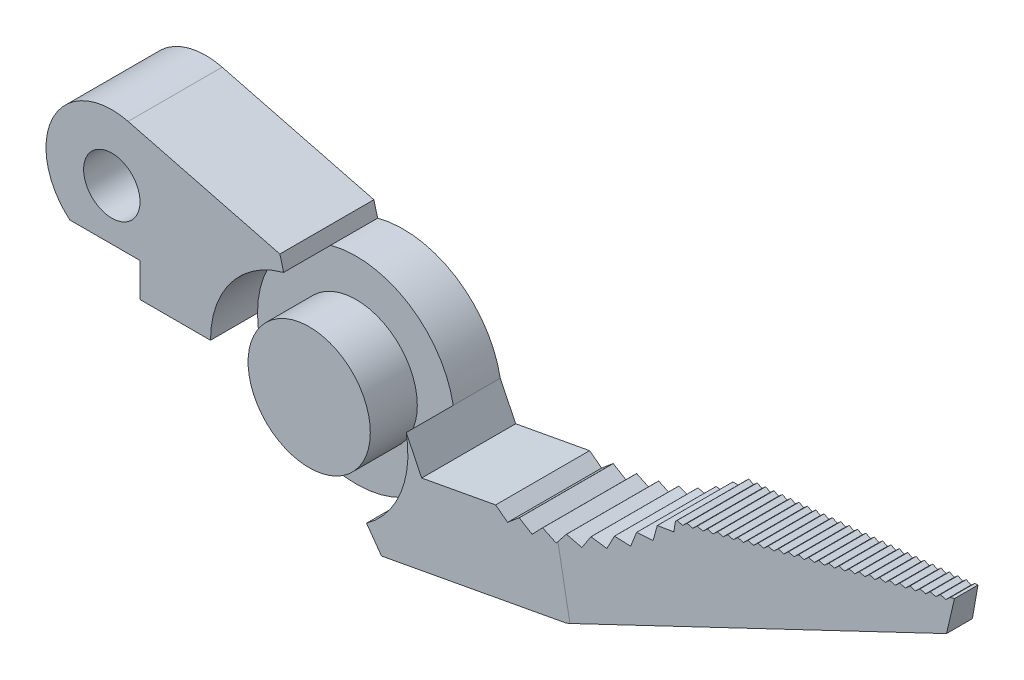
SolidWorks part; units mm, degrees
note: The reader was unsure of these and kept them because the rebuilt part matched: shared geometry of "Sketch1<3>", "Sketch1<4>".
ref_plane "Front Plane" through (0, 0, 0) normal (0, 0, 1) x (1, 0, 0)
ref_plane "Top Plane" through (0, 0, 0) normal (0, 1, 0) x (1, 0, 0)
ref_plane "Right Plane" through (0, 0, 0) normal (1, 0, 0) x (0, 0, -1)
sketch "Sketch1" plane through (0, 0, 0) normal (0, 0, 1) x (1, 0, 0)
  line L0 (-9.6304, 7.8902) -> (-1.5595, 5.82)
  line L2 (0, 0) -> (-1.5595, 5.82)
  line L3 (19.8321, 0) -> (0, 0) construction
  line L4 (0, 0) -> (0, 10.7679) construction
  line L5 (-12.7271, 1.8) -> (-9, 1.8)
  line L6 (-9, 1.8) -> (-9, 0)
  line L7 (-9, 0) -> (0, 0)
  line L8 (0, 0) -> (32.4474, 6.0138) construction
  line L9 (0, 0) -> (3.8444, -5.3897)
  line L10 (3.8444, -5.3897) -> (13.677, -3.5673)
  line L11 (13.677, -3.5673) -> (32.0857, 4.2505)
  line L12 (32.0857, 4.2505) -> (32.4474, 6.0138)
  line L13 (32.4474, 6.0138) -> (18.6818, 3.4625)
  line L14 (0, 0) -> (5.1621, 0.9567)
  line L15 (5.1621, 0.9567) -> (5.983, -0.7289)
  line L16 (5.983, -0.7289) -> (9.916, 0)
  line L17 (9.916, 0) -> (9.5867, 1.7768) construction
  circle A0 centre (0, 0) radius 5.25
  arc A1 (-9.6304, 7.8902) -> (-12.7271, 1.8) centre (-10.5, 4.5) ccw
  circle A2 centre (-10.5, 4.5) radius 1.5
  circle A3 centre (0, 0) radius 3.25
  arc A4 (9.916, 0) -> (18.6818, 3.4625) centre (10.2446, 11.9955) ccw
  dimension "D1" = 6.5
  dimension "D2" = 10.5
  dimension "D3" = 7
  dimension "D4" = 3
  dimension "D5" = 10.5
  dimension "D6" = 4.5
  dimension "D19" = 12
  dimension "D7" = 15
  dimension "D8" = 1.8
  dimension "D9" = 9
  dimension "D10" = 10.5
  dimension "D11" = 10
  dimension "D12" = 20
  dimension "D13" = 33
  dimension "D14" = 65
  dimension "D15" = 6
  dimension "D16" = 1.8
  dimension "D17" = 19
  dimension "D18" = 4
  dimension "D20" = 4.5
extrude "Boss-Extrude1" add sketch "Sketch1" along normal blind 5 contours L0 A1 L5 L6 L7 A0 L2 A2 | A4 L16 L15 A0 L9 L10 L11 L12 L13
extrude "Boss-Extrude2" add sketch "Sketch1<3>" along normal blind 2.5 contours A0
sketch "Sketch1<3>" plane through (0, 0, 0) normal (0, 0, 1) x (1, 0, 0) same geometry as "Sketch1"
extrude "Boss-Extrude3" add sketch "Sketch1<4>" along normal blind 5 contours A3
sketch "Sketch1<4>" plane through (0, 0, 0) normal (0, 0, 1) x (1, 0, 0) same geometry as "Sketch1"
sketch "Sketch2" plane through (0, 0, 0) normal (-0.1822, 0.9833, 0) x (0.9833, 0.1822, 0)
  line L0 (13, 0) -> (33, -1.875)
  line L1 (33, 0) -> (19, 0) construction
  line L2 (33, -5) -> (33, 0) construction
  line L3 (33, -1.875) -> (33, 0)
  line L4 (33, 0) -> (13, 0)
  line L5 (19, -2.5) -> (33, -2.5) construction
  line L6 (19, -5) -> (19, 0) construction
  line L7 (33, -3.125) -> (33, -5)
  line L8 (13, -5) -> (33, -3.125)
  line L9 (33, -5) -> (13, -5)
  dimension "D1" = 20
  dimension "D2" = 1.25
extrude "Cut-Extrude1" cut sketch "Sketch2" against normal through all
sketch "Sketch3" plane through (0, 0, 0) normal (0, 0, 1) x (1, 0, 0)
  line L0 (31.7591, 5.8862) -> (32.0323, 5.7843)
  line L1 (32.4474, 6.0138) -> (18.6818, 3.4625) construction
  line L2 (32.0323, 5.7843) -> (32.2508, 5.9773)
  line L3 (32.2508, 5.9773) -> (31.7591, 5.8862)
  point P6 (32.0049, 5.9318)
  dimension "D1" = 0.5
  dimension "D2" = 0.15
  dimension "D3" = 0.2
extrude "Cut-Extrude2" cut sketch "Sketch3" along normal through all and the other way through all
pattern_linear "LPattern1" count 28 spacing 0.5 along (-0.9833, -0.1822, 0) of "Cut-Extrude2"
sketch "Sketch4" plane through (0, 0, 0) normal (0, 0, 1) x (1, 0, 0)
  line L0 (9.916, 0) -> (11.1657, 0.0309)
  line L1 (9.916, 0) -> (10.5532, -0.4844)
  line L2 (10.5532, -0.4844) -> (11.1657, 0.0309)
  arc A0 (9.916, 0) -> (13.1558, 0.354) centre (10.2446, 11.9955) ccw construction
  dimension "D1" = 0.5
  dimension "D2" = 1.25
extrude "Cut-Extrude3" cut sketch "Sketch4" along normal through all
pattern_circular "CirPattern1" count 8 every 6 about axis through (10.2446, 11.9955, 0) along (0, 0, 1) of "Cut-Extrude3"
